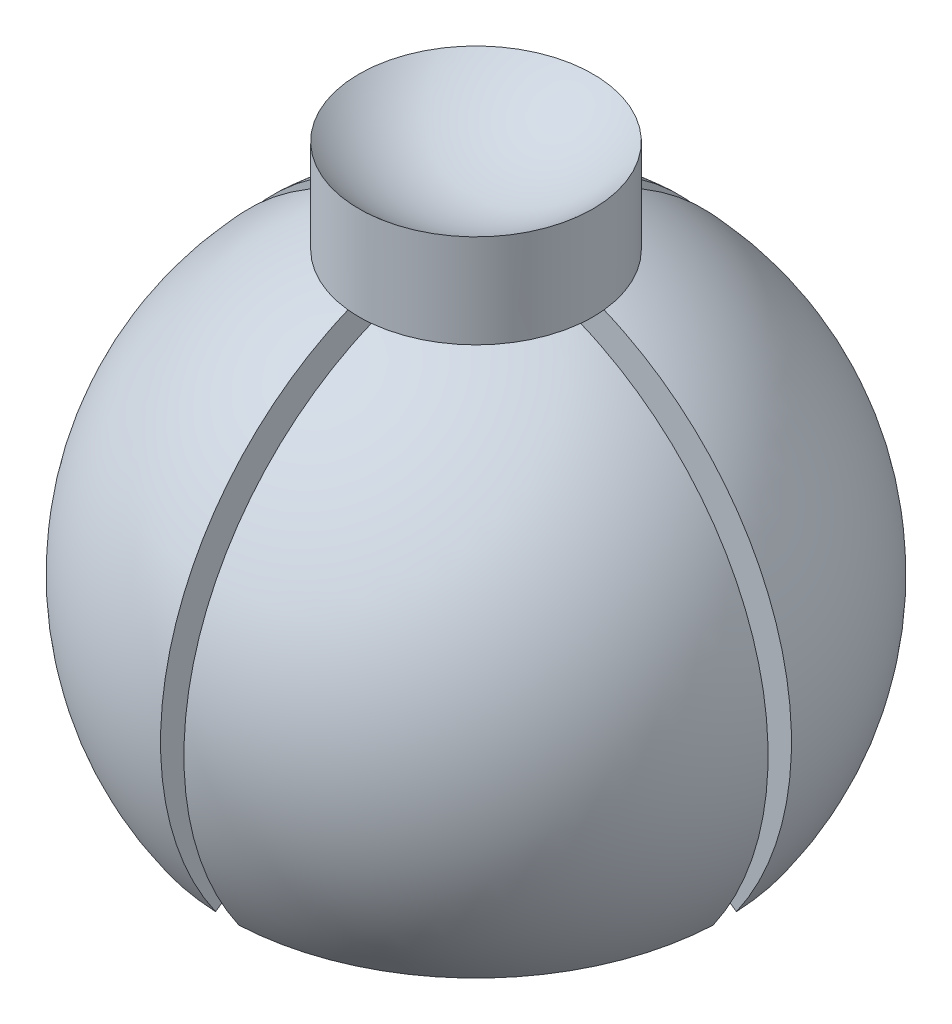
SolidWorks part; units mm, degrees
other "Markup1"
sketch "Sketch3" plane through (-5.9948, -3.4415, 5.9948) normal (0, 0, 1) x (1, 0, 0)
ref_plane "Front Plane" through (0, 0, 0) normal (0, 0, 1) x (1, 0, 0)
ref_plane "Top Plane" through (0, 0, 0) normal (0, 1, 0) x (1, 0, 0)
ref_plane "Right Plane" through (0, 0, 0) normal (1, 0, 0) x (0, 0, -1)
sketch "Sketch1" plane through (0, 0, 0) normal (0, 0, 1) x (1, 0, 0)
  line L1 (0, 7) -> (0, 5)
  line L4 (4.0958, -2.8679) -> (5.3245, -3.7282)
  line L5 (0, 0) -> (3.8805, 0) construction
  line L6 (0, 0) -> (4.0958, -2.8679) construction
  line L10 (2.5, 6) -> (2.5, 8)
  line L11 (0, 7) -> (-1.3019, 7) construction
  arc A0 (4.0958, -2.8679) -> (0, 5) centre (0, 0) ccw
  arc A1 (5.3245, -3.7282) -> (2.5, 6) centre (0, 0) ccw
  arc A2 (2.5, 8) -> (0, 7) centre (0, 10.625) cw
  dimension "D1" = 5
  dimension "D2" = 13
  dimension "D6" = 1
  dimension "D3" = 35
  dimension "D4" = 2.5
  dimension "D5" = 2
revolve "Revolve1" add sketch "Sketch1" angle 360 about L1
sketch "Sketch2" plane through (0, 0, 0) normal (0, 0, 1) x (1, 0, 0)
  line L0 (-0.25, -3.7282) -> (-0.25, 6)
  line L1 (-0.25, -3.7282) -> (0.25, -3.7282)
  line L2 (-0.25, 6) -> (0.25, 6)
  line L3 (0.25, -3.7282) -> (0.25, 6)
  line L4 (5.3245, -3.7282) -> (-5.3245, -3.7282) construction
  line L5 (-2.5, 6) -> (2.5, 6) construction
  point P6 (0, 6)
  dimension "D1" = 0.5
extrude "Cut-Extrude1" cut sketch "Sketch2" against normal blind 10
pattern_circular "CirPattern1" count 4 over 360 about axis through (0, -3.7282, 0) along (0, 1, 0) of "Cut-Extrude1"
